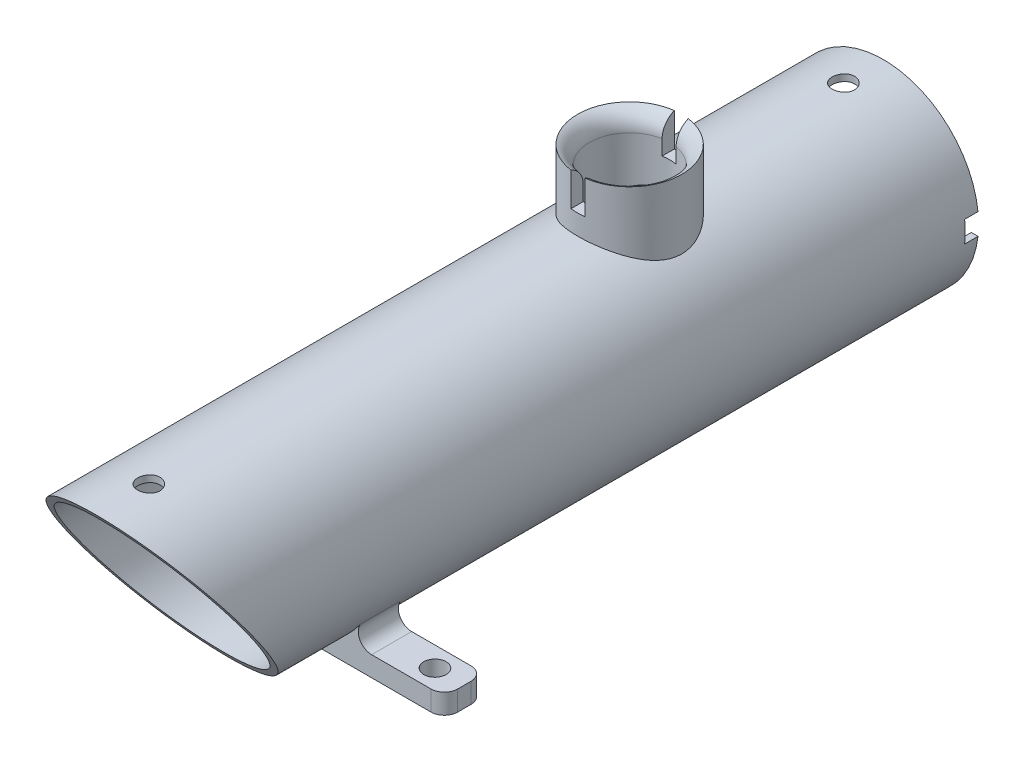
SolidWorks part; units mm, degrees
ref_plane "Front Plane" through (0, 0, 0) normal (0, 0, 1) x (1, 0, 0)
ref_plane "Top Plane" through (0, 0, 0) normal (0, 1, 0) x (1, 0, 0)
ref_plane "Right Plane" through (0, 0, 0) normal (1, 0, 0) x (0, 0, -1)
sketch "Sketch4" plane through (0, 0, 0) normal (0, 0, 1) x (1, 0, 0)
  circle A0 centre (0, 0) radius 14.25
  circle A1 centre (0, 0) radius 13.25
  dimension "D1" = 26.5
  dimension "D2" = 1
extrude "Boss-Extrude3" add sketch "Sketch4" along normal blind 118
sketch "Sketch5" plane through (0, 0, 118) normal (0, 0, 1) x (1, 0, 0)
  circle A0 centre (0, 0) radius 14.25 construction
  point P0 (0, 14.25)
  point P1 (14.25, 0)
  point P4 (-14.25, 0)
  point P5 (0, -14.25)
ref_plane "Plane1" through (0, 14.25, 118) normal (0, 1, 0) x (1, 0, 0)
sketch "Sketch6" plane through (0, 14.25, 118) normal (0, 1, 0) x (1, 0, 0)
  line L0 (-14.25, 0) -> (14.25, 0) construction
  circle A0 centre (0, 80) radius 6
  circle A1 centre (0, 80) radius 7.8
  dimension "D1" = 12
  dimension "D2" = 1.8
  dimension "D3" = 80
extrude "Boss-Extrude4" add sketch "Sketch6" along normal blind 8 and the other way blind 4
sketch "Sketch7" plane through (0, 22.25, 0) normal (0, 1, 0) x (1, 0, 0)
  circle A0 centre (0, -38) radius 6
  circle A1 centre (0, -38) radius 6 construction
extrude "Cut-Extrude1" cut sketch "Sketch7" against normal blind 20
sketch "Sketch8" plane through (0, 0, 118) normal (0, 0, 1) x (1, 0, 0)
  circle A0 centre (0, 0) radius 13.25
extrude "Cut-Extrude2" cut sketch "Sketch8" against normal up to surface (118 mm away) up to face at (14.25, 0, 0)
sketch "Sketch11" plane through (0, 14.25, 118) normal (0, 1, 0) x (1, 0, 0)
  line L0 (-14.25, 0) -> (14.25, 0) construction
  line L1 (13.25, 118) -> (-13.25, 118) construction
  circle A0 centre (0, 8) radius 1.675
  circle A1 centre (0, 112) radius 1.675
  dimension "D1" = 3.35
  dimension "D2" = 8
  dimension "D3" = 6
extrude "Cut-Extrude5" cut sketch "Sketch11" against normal blind 13
ref_plane "Plane5" through (0, -14.25, 118) normal (0, -1, 0) x (-1, 0, 0)
sketch "Sketch15" plane through (0, -14.25, 118) normal (0, -1, 0) x (-1, 0, 0)
  line L5 (0, 65) -> (0, 0) construction
  line L7 (0, 28) -> (-24.25, 28)
  line L13 (0, 28) -> (0, 34)
  line L14 (0, 34) -> (-24.25, 34)
  line L15 (-24.25, 28) -> (-24.25, 34)
  line L16 (-14.25, 118) -> (-14.25, 0) construction
  line L17 (-14.25, 0) -> (14.25, 0) construction
  line L18 (-24.25, 31) -> (0, 31) construction
  circle A2 centre (-19.85, 31) radius 1.675
  point P0 (0, 65)
  point P15 (0, 65)
  point P16 (0, 22.5)
  dimension "D4" = 3.35
  dimension "D6" = 5.6
  dimension "D1" = 10
  dimension "D2" = 6
  dimension "D3" = 28
fillet "Fillet2" radius 3 1 edges at (-6, 22.25, 38)
sketch "Sketch20" plane through (0, 14.25, 118) normal (0, 1, 0) x (1, 0, 0)
  line L1 (-1.05, 87.8) -> (1.05, 87.8)
  line L2 (-1.05, 87.8) -> (-1.05, 84.8)
  line L3 (-1.05, 84.8) -> (1.05, 84.8)
  line L4 (1.05, 87.8) -> (1.05, 84.8)
  line L5 (-1.05, 75.2) -> (1.05, 75.2)
  line L6 (-1.05, 75.2) -> (-1.05, 72.2)
  line L7 (-1.05, 72.2) -> (1.05, 72.2)
  line L8 (1.05, 75.2) -> (1.05, 72.2)
  circle A2 centre (0, 80) radius 7.8 construction
  circle A3 centre (0, 80) radius 4.7474
  circle A4 centre (0, 80) radius 6 construction
  point P14 (0, 75.2)
  point P15 (0, 84.8)
  dimension "D1" = 2.1
  dimension "D2" = 3
extrude "Boss-Extrude8" add sketch "Sketch15" against normal blind 3
sketch "Sketch27" plane through (0, 0, 0) normal (0, 0, -1) x (-1, 0, 0)
  circle A0 centre (0, 0) radius 13.25
extrude "Cut-Extrude15" cut sketch "Sketch27" against normal up to surface (118 mm away) up to face at (14.25, 0, 118)
sketch "Sketch29" plane through (0, 0, 0) normal (0, 0, -1) x (-1, 0, 0)
  line L1 (-17.6299, -1.6) -> (17.6299, -1.6)
  line L2 (-17.6299, -1.6) -> (-17.6299, 1.6)
  line L3 (-17.6299, 1.6) -> (17.6299, 1.6)
  line L4 (17.6299, -1.6) -> (17.6299, 1.6)
  line L5 (-17.6299, -1.6) -> (17.6299, 1.6) construction
  line L6 (-17.6299, 1.6) -> (17.6299, -1.6) construction
  point P0 (0, 0)
  dimension "D1" = 3.2
extrude "Cut-Extrude17" cut sketch "Sketch29" against normal blind 2
extrude "Cut-Extrude18" cut sketch "Sketch20" along normal blind 10 from offset 3 contours A3 L4 L1 L2 | A3 L6 L7 L8 region at (0, 14.25, 31.7) region at (0, 14.25, 44.3)
sketch "Sketch30" plane through (24.25, 0, 0) normal (1, 0, 0) x (0, 0, -1)
  line L0 (-118, 14.25) -> (-98.0441, -14.25)
  line L1 (-118, -14.25) -> (-90, -14.25) construction
  line L2 (-98.0441, -14.25) -> (-118, -14.25)
  line L3 (-118, -14.25) -> (-118, 14.25)
  dimension "D1" = 35
extrude "Cut-Extrude19" cut sketch "Sketch30" against normal blind 50
fillet "Fillet3" radius 2 3 edges at (8.7464, -11.25, 87) (24.25, -12.75, 90) (24.25, -12.75, 84)
